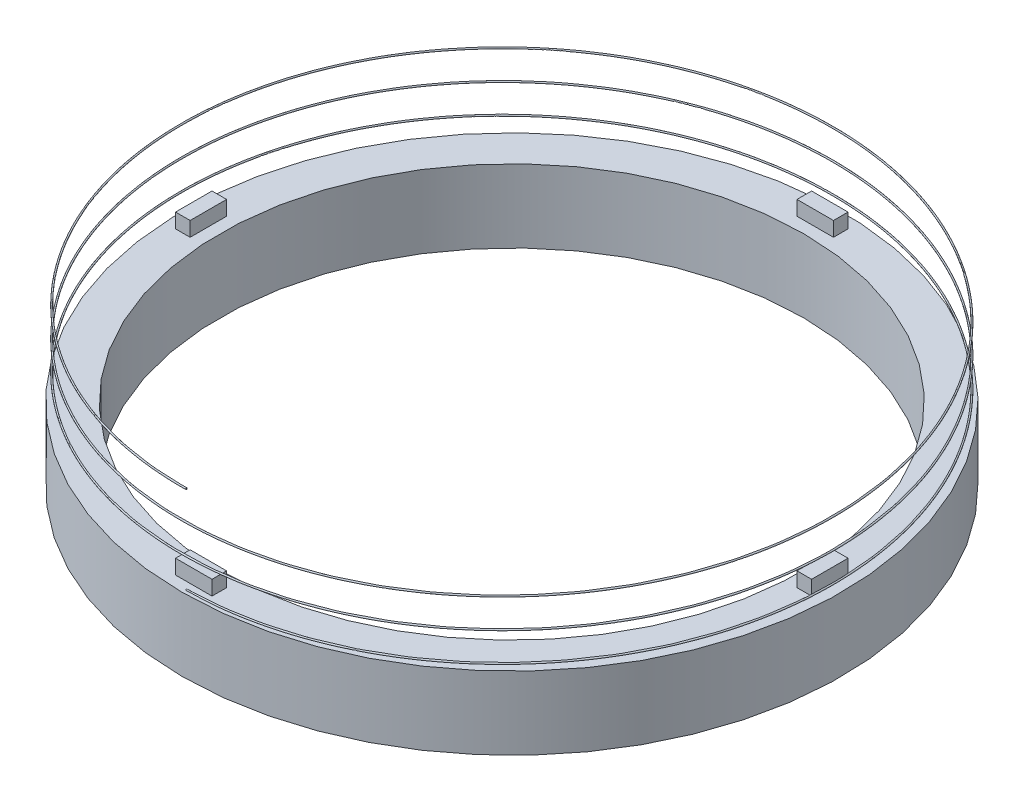
SolidWorks part; units mm, degrees
material "2024 Alloy"
ref_plane "Front Plane" through (0, 0, 0) normal (0, 0, 1) x (1, 0, 0)
ref_plane "Top Plane" through (0, 0, 0) normal (0, 1, 0) x (1, 0, 0)
ref_plane "Right Plane" through (0, 0, 0) normal (1, 0, 0) x (0, 0, -1)
sketch "Sketch2" plane through (0, 0, 0) normal (0, 1, 0) x (1, 0, 0)
  circle A0 centre (0, 0) radius 22.6
  circle A1 centre (0, 0) radius 20
  dimension "D1" = 45.2
  dimension "D2" = 40
extrude "Boss-Extrude2" add sketch "Sketch2" along normal blind 5
sketch "Sketch3" plane through (0, 5, 0) normal (0, 1, 0) x (1, 0, 0)
  line L1 (-1.25, -20.8) -> (1.25, -20.8)
  line L2 (-1.25, -20.8) -> (-1.25, -21.8)
  line L3 (-1.25, -21.8) -> (1.25, -21.8)
  line L4 (1.25, -20.8) -> (1.25, -21.8)
  point P4 (0, -20.8)
  dimension "D1" = 1
  dimension "D2" = 2.5
  dimension "D3" = 20.8
extrude "Boss-Extrude3" add sketch "Sketch3" along normal blind 1
pattern_circular "CirPattern1" count 4 over 360 about axis through (0, 5, 0) along (0, -1, 0) of "Boss-Extrude3"
sketch "Sketch4" plane through (0, 0, 0) normal (0, 1, 0) x (1, 0, 0)
  circle A0 centre (0, 0) radius 23.1
  dimension "D1" = 46.2
sketch "Sketch21" plane through (0, 5, 0) normal (0, 1, 0) x (1, 0, 0)
  circle A0 centre (0, 0) radius 22.3
  dimension "D1" = 44.6
curve "Helix/Spiral2" pitch 2 height 6 radius 22.3 centre (0, 5, 0) axis (0, 1, 0) start towards (0, 0, 1)
sweep "Sweep2" add path "Helix/Spiral2" circular profile diameter 0.1 parameters "D3"=0.1
